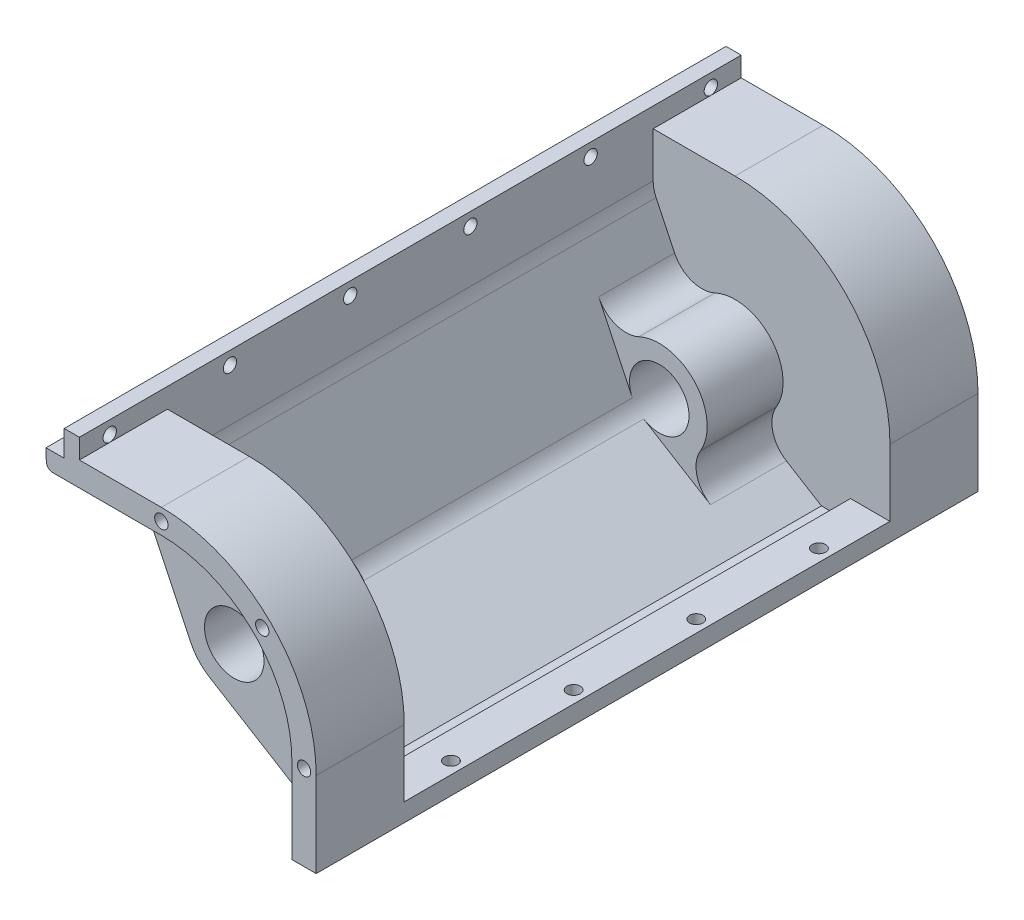
SolidWorks part; units mm, degrees
ref_plane "Спереди" through (0, 0, 0) normal (0, 0, 1) x (1, 0, 0)
ref_plane "Сверху" through (0, 0, 0) normal (0, 1, 0) x (1, 0, 0)
ref_plane "Справа" through (0, 0, 0) normal (1, 0, 0) x (0, 0, -1)
sketch "Эскиз1" plane through (0, 0, 0) normal (0, 0, 1) x (1, 0, 0)
  line L1 (-62, -308) -> (-94, -308) construction
  line L3 (-11, -390) -> (-11, -351) construction
  line L5 (-62, -308) -> (-94, -308)
  line L7 (-11, -379) -> (-11, -351)
  line L9 (-100, 200015.7119) -> (-100, -249984.2881) construction
  line L10 (-94, -308) -> (-100, -308)
  line L11 (-100, -308) -> (-100, -302)
  line L12 (-11, -379) -> (-19, -379)
  line L15 (10.8625, -379) -> (20.8625, -379) construction
  line L16 (-19, -390) -> (-19, -351) construction
  line L17 (-19, -379) -> (-19, -351)
  line L19 (-100, -302) -> (-94, -302) construction
  line L21 (-100, -302) -> (-94, -302)
  line L22 (-94, -305) -> (-94, -275.45) construction
  line L23 (-94, -302) -> (-94, -293.5)
  line L24 (-94, -293.5) -> (-89, -293.5)
  line L27 (-89, -293.5) -> (-89, -300)
  line L28 (-89, -300) -> (-62, -300)
  arc A0 (-19, -351) -> (-62, -308) centre (-62, -351) ccw construction
  arc A1 (-11, -351) -> (-62, -300) centre (-62, -351) ccw construction
  arc A2 (-19, -351) -> (-62, -308) centre (-62, -351) ccw
  arc A3 (-11, -351) -> (-62, -300) centre (-62, -351) ccw
  circle A7 centre (-62, -351) radius 38 construction
  dimension "D3" = 76
  dimension "D4" = 6.5
  dimension "D5" = 5
extrude "Бобышка-Вытянуть1" add sketch "Эскиз1" along normal offset from surface (24 mm away) 30
sketch "Эскиз3" plane through (0, 0, 24) normal (0, 0, 1) x (1, 0, 0)
  line L0 (-19, -379) -> (-19, -385)
  line L2 (-36.7149, -385) -> (-70.2481, -364.4763)
  line L3 (-76.2625, -357.7985) -> (-100, -308)
  line L4 (-19, -385) -> (-28.7149, -385)
  line L5 (-28.7149, -385) -> (-28.7149, -390)
  line L6 (-28.7149, -390) -> (-36.7149, -390)
  line L7 (-36.7149, -390) -> (-36.7149, -385)
  line L8 (96.5, -390) -> (-15.5, -390) construction
  line L9 (-28.7149, -385) -> (-36.7149, -385)
  line L10 (-100, -308) -> (-62, -308)
  line L11 (-19, -351) -> (-19, -379)
  line L12 (-19, -379) -> (-11, -379)
  line L13 (-11, -379) -> (-11, -351)
  line L14 (-62, -300) -> (-89, -300)
  line L15 (-89, -300) -> (-89, -293.5)
  line L16 (-89, -293.5) -> (-94, -293.5)
  line L17 (-94, -293.5) -> (-94, -302)
  line L18 (-94, -302) -> (-100, -302)
  line L19 (-100, -302) -> (-100, -308)
  line L22 (-19, -379) -> (-11, -379)
  line L23 (-11, -379) -> (-11, -351)
  line L24 (-62, -300) -> (-89, -300)
  line L25 (-89, -300) -> (-89, -293.5)
  line L26 (-89, -293.5) -> (-94, -293.5)
  line L27 (-94, -293.5) -> (-94, -302)
  line L28 (-94, -302) -> (-100, -302)
  line L29 (-100, -302) -> (-100, -308)
  line L30 (-27.3398, -404.054) -> (-141.6582, -362.4455) construction
  line L31 (0, 0) -> (-50000, 0) construction
  line L32 (-89, -300) -> (-89, -317.1326)
  line L33 (-11, -373) -> (-24, -373)
  line L34 (-24, -373) -> (-24, -379.8824)
  line L35 (-24, -379.8824) -> (-33.5827, -379.8824)
  line L36 (-33.5827, -379.8824) -> (-67.1159, -359.3587)
  line L37 (-70.8464, -355.2168) -> (-89, -317.1326)
  line L38 (-70.8464, -355.2168) -> (-94.5838, -305.4183) construction
  circle A0 centre (-62, -351) radius 9.8
  circle A1 centre (-62, -351) radius 15.8 construction
  arc A2 (-19, -351) -> (-62, -308) centre (-62, -351) ccw
  arc A3 (-11, -351) -> (-62, -300) centre (-62, -351) ccw
  arc A5 (-11, -351) -> (-62, -300) centre (-62, -351) ccw
  arc A6 (-76.2625, -357.7985) -> (-70.2481, -364.4763) centre (-62, -351) ccw
  circle A7 centre (-62, -351) radius 38 construction
  arc A8 (-70.8464, -355.2168) -> (-67.1159, -359.3587) centre (-62, -351) ccw
  line M21 (-100, -308) -> (-62, -308)
  arc M22 (-62, -308) -> (-19, -351) centre (-62, -351) cw
  line M23 (-19, -351) -> (-19, -379)
  line M24 (-19, -379) -> (-11, -379)
  line M25 (-11, -379) -> (-11, -351)
  arc M26 (-11, -351) -> (-62, -300) centre (-62, -351) ccw
  line M27 (-62, -300) -> (-89, -300)
  line M28 (-89, -300) -> (-89, -293.5)
  line M29 (-89, -293.5) -> (-94, -293.5)
  line M30 (-94, -293.5) -> (-94, -302)
  line M31 (-94, -302) -> (-100, -302)
  line M32 (-100, -302) -> (-100, -308)
  dimension "D2" = 19.6
  dimension "D4" = 76
  dimension "D11" = 31.6
  dimension "D5" = 20
  dimension "D6" = 10
  dimension "D7" = 8
  dimension "D8" = 6
  dimension "D9" = 5
  dimension "D3" = 6
  dimension "D10" = 6
extrude "Бобышка-Вытянуть2" add sketch "Эскиз3" along normal blind 5 contours L33 L23 L32 M26 M27 M21 M22 M23 | A0 L36 L35 L34 L33 L32 L37 M23 M22 M21 | L3 A6 L2 L9 L4 L0 L33 L34 L35 L36 A0 L37 L32 M23 M21 | L5 L9 L7 L6 | L32 M28 M29 M30 M31 M32 M21 | L33 M25 M23 M24 region at (-20.1176, -382, 24) region at (-15, -376, 24) region at (-49.2103, -339.0861, 24) region at (-17.9317, -362, 24) region at (-32.7149, -387.5, 24) region at (-93.3249, -302.1601, 24)
extrude "Бобышка-Вытянуть3" add sketch "Эскиз3<4>" along normal up to surface (85 mm away) contours L3 A6 L2 L9 L4 L0 L33 L34 L35 L36 A0 L37 L32 M23 M21 | L32 M28 M29 M30 M31 M32 M21 | L33 M25 M23 M24 region at (-20.1176, -382, 24) region at (-15, -376, 24) region at (-93.3249, -302.1601, 24)
sketch "Эскиз3<4>" plane through (0, 0, 24) normal (0, 0, 1) x (1, 0, 0) same geometry as "Эскиз3"
extrude "Бобышка-Вытянуть5" add sketch "Эскиз3<5>" along normal blind 30 contours L5 L9 L7 L6 region at (-32.7149, -387.5, 24)
sketch "Эскиз3<5>" plane through (0, 0, 24) normal (0, 0, 1) x (1, 0, 0) same geometry as "Эскиз3"
sketch "Эскиз4" plane through (0, 0, 24) normal (0, 0, -1) x (-1, 0, 0)
  circle A0 centre (62, -351) radius 9.8 construction
  arc A1 (70.2481, -364.4763) -> (76.2625, -357.7985) centre (62, -351) ccw construction
  circle A2 centre (62, -351) radius 9.8
  circle A4 centre (62, -351) radius 15.8
extrude "Бобышка-Вытянуть4" add sketch "Эскиз4" against normal blind 30
fillet "Скругление1" radius 10 3 edges at (-89, -317.1326, 69) (-76.1792, -344.0292, 41.5) (-56.5451, -365.8285, 41.5)
fillet "Скругление2" radius 4.5 2 edges at (-28.7149, -385, 39) (-36.7149, -385, 39)
fillet "Скругление3" radius 20 1 edges at (-100, -308, 66.5) tangent propagation no
fillet "Скругление4" radius 8 1 edges at (-36.7149, -385, 81.5) tangent propagation no
fillet "Скругление5" radius 2 1 edges at (-99.4819, -308, 12)
sketch "Эскиз5" plane through (-94, 0, 0) normal (-1, 0, 0) x (0, 0, 1)
  line L0 (0, -293.5) -> (0, -302) construction
  line L1 (128.8, -297.75) -> (89.2, -297.75) construction
  line L4 (109, -302) -> (109, -293.5) construction
  line L5 (89.2, -297.75) -> (49.6, -297.75) construction
  line L6 (49.6, -297.75) -> (10, -297.75) construction
  circle A0 centre (89.2, -297.75) radius 2.2
  circle A1 centre (10, -297.75) radius 2.2
  circle A2 centre (49.6, -297.75) radius 2.2
  point P11 (109, -297.75)
  dimension "D2" = 4.4
  dimension "D1" = 10
extrude "Вырез-Вытянуть1" cut sketch "Эскиз5" against normal through all both and the other way through all
sketch "Эскиз7" plane through (0, -379, 0) normal (0, -1, 0) x (1, 0, 0)
  line L0 (-15, 129.2) -> (-15, 88.8) construction
  line L2 (-11, 109) -> (-19, 109) construction
  line L3 (-15, 88.8) -> (-15, 48.4) construction
  line L4 (-15, 48.4) -> (-15, 8) construction
  line L5 (-19, 0) -> (-11, 0) construction
  circle A0 centre (-15, 88.8) radius 2.2
  circle A1 centre (-15, 48.4) radius 2.2
  circle A2 centre (-15, 8) radius 2.2
  point P3 (-15, 109)
  dimension "D2" = 4.4
  dimension "D1" = 8
extrude "Вырез-Вытянуть2" cut sketch "Эскиз7" against normal blind 10
sketch "Эскиз8" plane through (0, 0, 0) normal (0, 0, -1) x (-1, 0, 0)
  line L0 (62, -300) -> (62, -308) construction
  line L1 (62, -351) -> (62, -304) construction
  line L2 (62, -351) -> (28.766, -317.766) construction
  circle A0 centre (62, -304) radius 2.2
  circle A1 centre (28.766, -317.766) radius 2.2
  circle A2 centre (15, -351) radius 2.2
  circle A3 centre (62, -351) radius 9.8 construction
  dimension "D1" = 4.4
  dimension "D3" = 45
  dimension "D2" = 3
extrude "Вырез-Вытянуть3" cut sketch "Эскиз8" against normal blind 10
mirror "Зеркальное отражение1" about plane through (0, 0, 109) normal (0, 0, -1) of bodies 111
equation "\"D1@Бобышка-Вытянуть1\"=24+1+2+3"
equation "\"D2@Эскиз3\"=12+4*2-0.4"
